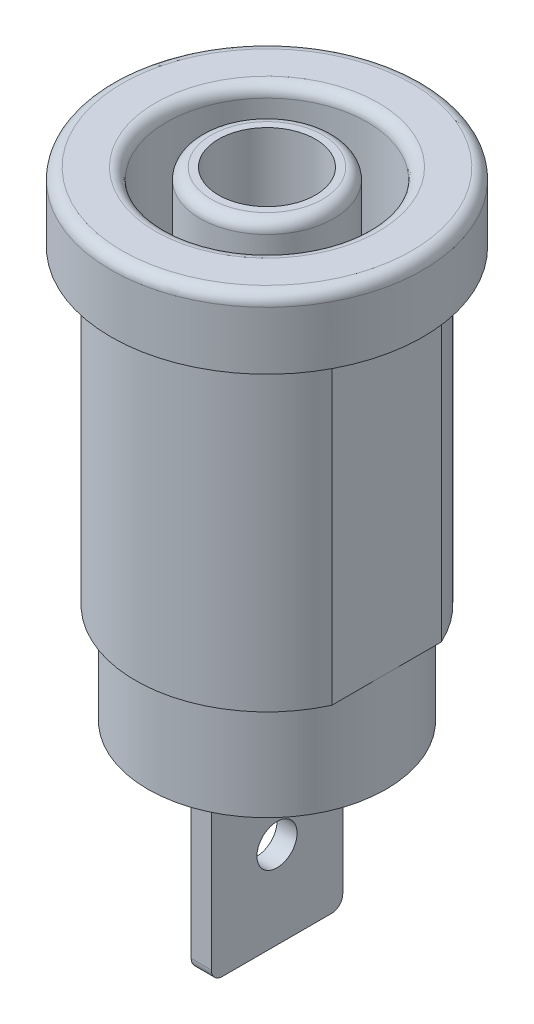
SolidWorks part; units mm, degrees
ref_plane "Front Plane" through (0, 0, 0) normal (0, 0, 1) x (1, 0, 0)
ref_plane "Top Plane" through (0, 0, 0) normal (0, 1, 0) x (1, 0, 0)
ref_plane "Right Plane" through (0, 0, 0) normal (1, 0, 0) x (0, 0, -1)
sketch "Sketch1" plane through (0, 0, 0) normal (0, 1, 0) x (1, 0, 0)
  line L1 (5.365, -66.9155) -> (-5.365, -66.9155)
  line L2 (5.365, -66.9155) -> (5.365, 66.9155)
  line L3 (5.365, 66.9155) -> (-5.365, 66.9155)
  line L4 (-5.365, -66.9155) -> (-5.365, 66.9155)
  line L5 (5.365, -66.9155) -> (-5.365, 66.9155) construction
  line L6 (5.365, 66.9155) -> (-5.365, -66.9155) construction
  line L7 (0.45, -2.95) -> (-0.45, -2.95)
  line L8 (0.45, -2.95) -> (0.45, 2.95)
  line L9 (0.45, 2.95) -> (-0.45, 2.95)
  line L10 (-0.45, -2.95) -> (-0.45, 2.95)
  line L11 (0.45, -2.95) -> (-0.45, 2.95) construction
  line L12 (0.45, 2.95) -> (-0.45, -2.95) construction
  circle A0 centre (0, 0) radius 5.9
  circle A1 centre (0, 0) radius 5.35
  circle A2 centre (0, 0) radius 7
  circle A3 centre (0, 0) radius 3
  point P0 (0, 0)
  dimension "D2" = 11.8
  dimension "D3" = 10.7
  dimension "D4" = 14
  dimension "D7" = 6
  dimension "D1" = 10.73
  dimension "D5" = 5.9
  dimension "D6" = 0.9
extrude "Boss-Extrude1" add sketch "Sketch1" against normal blind 30 contours L8 L9 L10 L7
extrude "Boss-Extrude2" add sketch "Sketch1<3>" against normal blind 21.51 contours A3 L7 L10 L9 L8 region at (-2.9151, 0, 0)
sketch "Sketch1<3>" plane through (0, 0, 0) normal (0, 1, 0) x (1, 0, 0) same geometry as "Sketch1"
extrude "Boss-Extrude3" add sketch "Sketch1<4>" against normal blind 21.5 contours A1 A3 region at (-5.1987, 0, 0)
sketch "Sketch1<4>" plane through (0, 0, 0) normal (0, 1, 0) x (1, 0, 0) same geometry as "Sketch1"
extrude "Boss-Extrude4" add sketch "Sketch1<5>" against normal blind 17 contours L2 A0 L4 A1 region at (0, 0, 5.7405)
sketch "Sketch1<5>" plane through (0, 0, 0) normal (0, 1, 0) x (1, 0, 0) same geometry as "Sketch1"
extrude "Boss-Extrude5" add sketch "Sketch1<6>" against normal blind 3.1 contours L4 A2 L2 A0 | L4 A0 | L4 A2 A0 | L2 A2 L4 A0 | L2 A2 A0 | L2 A0 region at (0, 0, 6.8835) region at (6.1212, 0, 0) region at (-6.1212, 0, 0) region at (5.5799, 0, 0) region at (-5.5799, 0, 0) region at (0, 0, -6.8835)
sketch "Sketch1<6>" plane through (0, 0, 0) normal (0, 1, 0) x (1, 0, 0) same geometry as "Sketch1"
sketch "Sketch2" plane through (0, 0, 0) normal (0, 1, 0) x (1, 0, 0)
  circle A0 centre (0, 0) radius 4.5
  circle A1 centre (0, 0) radius 3
  dimension "D1" = 9
  dimension "D2" = 6
extrude "Cut-Extrude1" cut sketch "Sketch2" against normal blind 19.5
sketch "Sketch3" plane through (0, 0, 0) normal (0, 1, 0) x (1, 0, 0)
  circle A0 centre (0, 0) radius 2.175
  dimension "D1" = 4.35
extrude "Cut-Extrude2" cut sketch "Sketch3" against normal blind 4.1
sketch "Sketch4" plane through (0, -4.1, 0) normal (0, 1, 0) x (1, 0, 0)
  circle A0 centre (0, 0) radius 2.1
  dimension "D1" = 4.2
extrude "Cut-Extrude3" cut sketch "Sketch4" against normal blind 15.9
sketch "Sketch5" plane through (-0.45, 0, 0) normal (-1, 0, 0) x (0, 0, 1)
  line L0 (-2.95, -30) -> (-2.95, -21.51) construction
  line L1 (2.95, -30) -> (-2.95, -30) construction
  circle A0 centre (0, -26.1) radius 0.9
  dimension "D1" = 1.8
  dimension "D2" = 2.95
  dimension "D3" = 3.9
extrude "Cut-Extrude4" cut sketch "Sketch5" against normal through all
fillet "Fillet1" radius 0.5 5 edges at (0, 0, 3) (0, 0, 4.5) (0, 0, 7) (0, -30, 2.95) (0, -30, -2.95)
